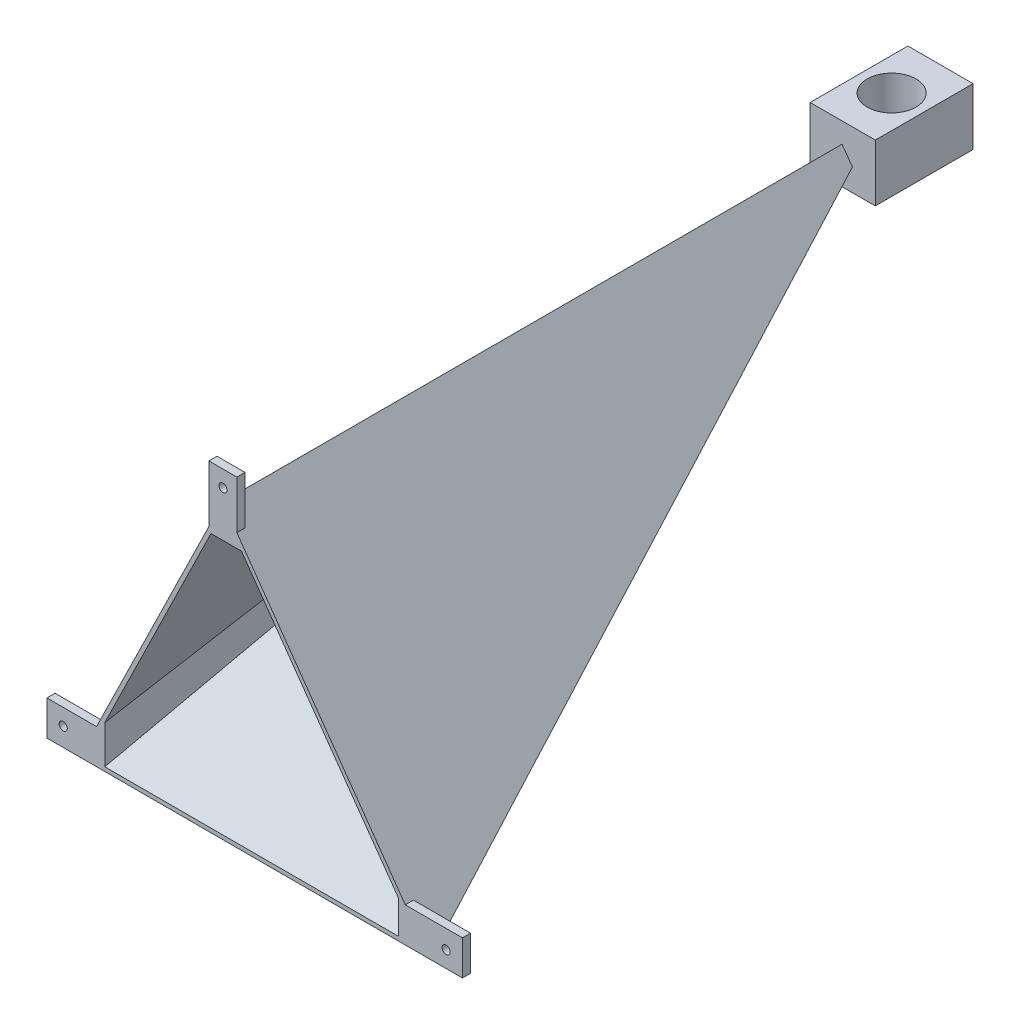
SolidWorks part; units mm, degrees
ref_plane "Plano frontal" through (0, 0, 0) normal (0, 0, 1) x (1, 0, 0)
ref_plane "Plano superior" through (0, 0, 0) normal (0, 1, 0) x (1, 0, 0)
ref_plane "Plano direito" through (0, 0, 0) normal (1, 0, 0) x (0, 0, -1)
sketch "Esboço2" plane through (0, 0, 0) normal (0, 0, 1) x (1, 0, 0)
  line L0 (-10.8631, 0) -> (204.1369, 0)
  line L1 (204.1369, 0) -> (77.102, 179.6166)
  line L2 (77.102, 179.6166) -> (-10.8631, 0)
  dimension "D1" = 215
  dimension "D2" = 220
  dimension "D3" = 200
ref_plane "Plano3" through (0, 0, -400) normal (0, 0, 1) x (1, 0, 0)
sketch "Esboço6" plane through (0, 0, -400) normal (0, 0, 1) x (1, 0, 0)
  point P0 (77.102, 179.6166)
loft "Loft1" add profiles "Esboço6", "Esboço2"
ref_plane "Plano5" through (77.102, 179.6166, -400) normal (0, 0, 1) x (1, 0, 0)
sketch "Esboço7" plane through (77.102, 179.6166, -400) normal (0, 0, 1) x (1, 0, 0)
  line L1 (-20, -17.5) -> (20, -17.5)
  line L2 (-20, -17.5) -> (-20, 17.5)
  line L3 (-20, 17.5) -> (20, 17.5)
  line L4 (20, -17.5) -> (20, 17.5)
  line L5 (-20, -17.5) -> (20, 17.5) construction
  line L6 (-20, 17.5) -> (20, -17.5) construction
  point P0 (0, 0)
  point P1 (0, 0)
  dimension "D1" = 35
  dimension "D2" = 40
extrude "Corte-extrusão3" cut sketch "Esboço7" along normal blind 20
sketch "Esboço8" plane through (0, 0, -380) normal (0, 0, -1) x (-1, 0, 0)
  line L1 (-97.5, 192) -> (-57.5, 192)
  line L2 (-97.5, 192) -> (-97.5, 157)
  line L3 (-97.5, 157) -> (-57.5, 157)
  line L4 (-57.5, 192) -> (-57.5, 157)
  line L5 (-97.5, 192) -> (-57.5, 157) construction
  line L6 (-97.5, 157) -> (-57.5, 192) construction
  point P0 (-77.5, 174.5)
  point P3 (-77.5, 174.5)
  dimension "D1" = 35
  dimension "D2" = 40
extrude "Ressalto-extrusão1" add sketch "Esboço8" along normal blind 60
sketch "Esboço9" plane through (0, 192, 0) normal (0, 1, 0) x (1, 0, 0)
  line L0 (97.5, 440) -> (97.5, 380) construction
  line L1 (57.5, 440) -> (97.5, 440) construction
  circle A0 centre (77.5, 410) radius 15
  dimension "D1" = 30
  dimension "D2" = 20
  dimension "D3" = 30
extrude "Corte-extrusão4" cut sketch "Esboço9" against normal blind 30
sketch "Esboço10" plane through (0, 0, 0) normal (0, 0, 1) x (1, 0, 0)
  line L1 (-40.8631, -21.3343) -> (19.1369, -21.3343)
  line L2 (-40.8631, -21.3343) -> (-40.8631, 21.3343)
  line L3 (-40.8631, 21.3343) -> (19.1369, 21.3343)
  line L4 (19.1369, -21.3343) -> (19.1369, 21.3343)
  line L5 (-40.8631, -21.3343) -> (19.1369, 21.3343) construction
  line L6 (-40.8631, 21.3343) -> (19.1369, -21.3343) construction
  point P0 (-10.8631, 0)
  dimension "D1" = 60
extrude "Corte-extrusão6" cut sketch "Esboço10" against normal blind 5
sketch "Esboço12" plane through (0, 0, -5) normal (0, 0, 1) x (1, 0, 0)
  line L0 (19.1369, 0) -> (19.1369, 21.3343)
  line L1 (19.1369, 0) -> (-30.8631, 0)
  line L2 (19.1369, 21.3343) -> (-30.8631, 21.3343)
  line L3 (-30.8631, 0) -> (-30.8631, 21.3343)
  dimension "D1" = 50
extrude "Ressalto-extrusão3" add sketch "Esboço12" along normal blind 5
sketch "Esboço13" plane through (0, 0, 0) normal (0, 0, 1) x (1, 0, 0)
  line L1 (234.1369, -21.3343) -> (174.1369, -21.3343)
  line L2 (234.1369, -21.3343) -> (234.1369, 21.3343)
  line L3 (234.1369, 21.3343) -> (174.1369, 21.3343)
  line L4 (174.1369, -21.3343) -> (174.1369, 21.3343)
  line L5 (234.1369, -21.3343) -> (174.1369, 21.3343) construction
  line L6 (234.1369, 21.3343) -> (174.1369, -21.3343) construction
  point P0 (204.1369, 0)
  dimension "D1" = 60
extrude "Corte-extrusão8" cut sketch "Esboço13" against normal blind 5
sketch "Esboço14" plane through (0, 0, -5) normal (0, 0, 1) x (1, 0, 0)
  line L0 (174.1369, 0) -> (174.1369, 21.3343)
  line L1 (174.1369, 0) -> (224.1369, 0)
  line L2 (174.1369, 21.3343) -> (224.1369, 21.3343)
  line L3 (224.1369, 0) -> (224.1369, 21.3343)
  dimension "D1" = 50
extrude "Ressalto-extrusão4" add sketch "Esboço14" along normal blind 5
sketch "Esboço15" plane through (0, 0, 0) normal (0, 0, 1) x (1, 0, 0)
  line L0 (97.5, 157) -> (57.5, 157) construction
  line L1 (68.514, 202.2333) -> (85.6901, 202.2333)
  line L2 (68.514, 202.2333) -> (68.514, 157)
  line L3 (68.514, 157) -> (85.6901, 157)
  line L4 (85.6901, 202.2333) -> (85.6901, 157)
  line L5 (68.514, 202.2333) -> (85.6901, 157) construction
  line L6 (68.514, 157) -> (85.6901, 202.2333) construction
  point P0 (77.102, 179.6166)
extrude "Corte-extrusão9" cut sketch "Esboço15" against normal blind 5
sketch "Esboço16" plane through (0, 0, -5) normal (0, 0, 1) x (1, 0, 0)
  line L0 (68.514, 157) -> (85.6901, 157)
  line L1 (68.514, 157) -> (68.514, 197)
  line L2 (85.6901, 157) -> (85.6901, 197)
  line L3 (68.514, 197) -> (85.6901, 197)
  dimension "D1" = 40
extrude "Ressalto-extrusão5" add sketch "Esboço16" along normal blind 5
sketch "Esboço17" plane through (0, 0, 0) normal (0, 0, 1) x (1, 0, 0)
  line L0 (-0.4149, 21.3343) -> (-30.8631, 21.3343) construction
  line L2 (-30.8631, 21.3343) -> (-30.8631, 0) construction
  line L3 (224.1369, 0) -> (224.1369, 21.3343) construction
  line L4 (174.1369, 0) -> (224.1369, 0) construction
  line L5 (85.6901, 167.4738) -> (85.6901, 197) construction
  line L6 (85.6901, 197) -> (68.514, 197) construction
  circle A0 centre (-20.8631, 11.3343) radius 2.5
  circle A1 centre (214.1369, 10) radius 2.5
  circle A2 centre (77.1901, 187) radius 2.5
  dimension "D1" = 5
  dimension "D4" = 5
  dimension "D9" = 5
  dimension "D2" = 10
  dimension "D3" = 10
  dimension "D5" = 10
  dimension "D6" = 10
  dimension "D7" = 8.5
  dimension "D8" = 10
extrude "Corte-extrusão10" cut sketch "Esboço17" against normal blind 10
sketch "Esboço18" plane through (0, 0, 0) normal (0, 0, 1) x (1, 0, 0)
  line L0 (-6.855, 2.5) -> (199.3067, 2.5)
  line L2 (199.3067, 2.5) -> (77.494, 174.7329)
  line L4 (77.494, 174.7329) -> (-6.855, 2.5)
  line L5 (19.1369, 0) -> (174.1369, 0) construction
  line L6 (189.0481, 21.3343) -> (85.6901, 167.4738) construction
  line L7 (68.514, 162.0806) -> (-0.4149, 21.3343) construction
  line L8 (2.3789, 21.3548) -> (2.3789, 2.5)
  line L9 (183.9355, 24.2335) -> (183.9355, 2.5)
  line L10 (69.0002, 157.3894) -> (89.7603, 157.3894)
  dimension "D1" = 2.5
  dimension "D2" = 2.5
  dimension "D3" = 2.5
sketch "Esboço20" plane through (0, 0, 0) normal (0, 0, 1) x (1, 0, 0)
  line L0 (4.6495, 2.5) -> (184.872, 2.5)
  line L1 (184.872, 2.5) -> (184.872, 22.9095)
  line L2 (184.872, 22.9095) -> (88.5717, 159.07)
  line L3 (19.1369, 0) -> (174.1369, 0) construction
  line L4 (189.0481, 21.3343) -> (85.6901, 167.4738) construction
  line L5 (88.5717, 159.07) -> (69.8232, 159.07)
  line L6 (85.6901, 197) -> (68.514, 197) construction
  line L7 (224.1369, 0) -> (224.1369, 21.3343) construction
  line L8 (4.6495, 2.5) -> (4.6495, 25.9911)
  line L9 (4.6495, 25.9911) -> (69.8232, 159.07)
  line L10 (68.514, 162.0806) -> (-0.4149, 21.3343) construction
  dimension "D1" = 2.5
  dimension "D2" = 2.5
  dimension "D3" = 2.5
loft "Loft de corte2" cut profiles "Esboço20", "Esboço6<3>"
sketch "Esboço6<3>" plane through (0, 0, -400) normal (0, 0, 1) x (1, 0, 0) same geometry as "Esboço6"
sketch "Esboço21" plane through (0, 157, 0) normal (0, -1, 0) x (1, 0, 0)
  line L0 (97.5, -440) -> (97.5, -380) construction
  line L2 (97.5, -440) -> (57.5, -440) construction
  circle A0 centre (77.5, -410) radius 2.5
  dimension "D1" = 20
  dimension "D2" = 30
  dimension "D3" = 5
extrude "Corte-extrusão11" cut sketch "Esboço21" against normal through all
